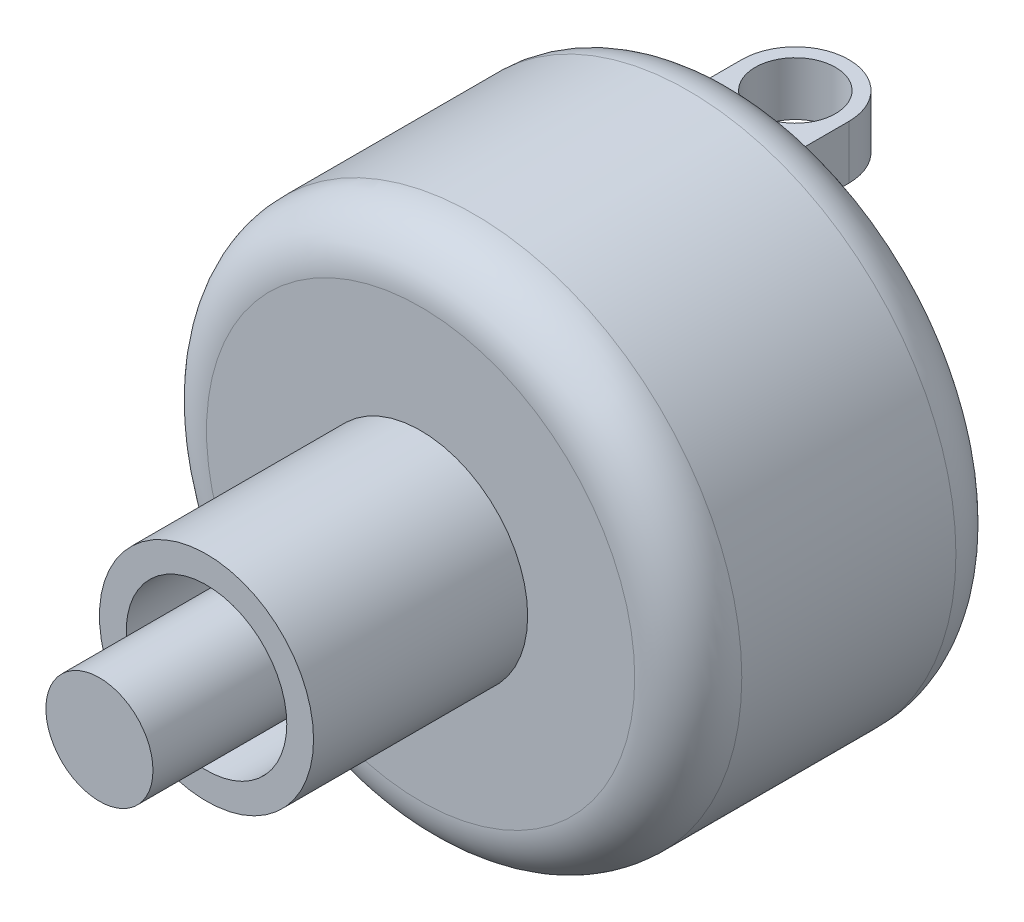
SolidWorks part; units mm, degrees
ref_plane "Front Plane" through (0, 0, 0) normal (0, 0, 1) x (1, 0, 0)
ref_plane "Top Plane" through (0, 0, 0) normal (0, 1, 0) x (1, 0, 0)
ref_plane "Right Plane" through (0, 0, 0) normal (1, 0, 0) x (0, 0, -1)
sketch "Sketch1" plane through (0, 0, 0) normal (0, 0, 1) x (1, 0, 0)
  circle A0 centre (0, 0) radius 25
  dimension "D1" = 50
extrude "Boss-Extrude1" add sketch "Sketch1" along normal blind 30
sketch "Sketch2" plane through (0, 0, 30) normal (0, 0, 1) x (1, 0, 0)
  circle A0 centre (0, 0) radius 10
  dimension "D1" = 20
extrude "Boss-Extrude2" add sketch "Sketch2" along normal blind 20
sketch "Sketch3" plane through (0, 0, 50) normal (0, 0, 1) x (1, 0, 0)
  circle A0 centre (0, 0) radius 7.5
  dimension "D1" = 15
extrude "Cut-Extrude1" cut sketch "Sketch3" against normal blind 20
sketch "Sketch4" plane through (0, 0, 30) normal (0, 0, 1) x (1, 0, 0)
  circle A0 centre (0, 0) radius 5
  dimension "D1" = 10
extrude "Boss-Extrude3" add sketch "Sketch4" along normal blind 30
sketch "Sketch5" plane through (0, 0, 0) normal (0, 0, -1) x (-1, 0, 0)
  circle A0 centre (0, 0) radius 7.5
  dimension "D1" = 15
extrude "Boss-Extrude4" add sketch "Sketch5" along normal blind 5
sketch "Sketch7" plane through (0, 0, 0) normal (0, 0, -1) x (-1, 0, 0)
  line L1 (5, 15) -> (-5, 15)
  line L2 (5, 15) -> (5, 20)
  line L3 (5, 20) -> (-5, 20)
  line L4 (-5, 15) -> (-5, 20)
  line L5 (5, -20) -> (-5, -20)
  line L6 (5, -20) -> (5, -15)
  line L7 (5, -15) -> (-5, -15)
  line L8 (-5, -20) -> (-5, -15)
  point P8 (0, 15)
  point P10 (0, -15)
  dimension "D1" = 5
  dimension "D2" = 10
  dimension "D3" = 10
  dimension "D4" = 5
  dimension "D5" = 15
  dimension "D6" = 15
extrude "Boss-Extrude5" add sketch "Sketch7" along normal blind 10
sketch "Sketch8" plane through (0, 20, 0) normal (0, 1, 0) x (1, 0, 0)
  line L0 (-5, 10) -> (5, 10) construction
  line L1 (5, 10) -> (5, 0) construction
  circle A0 centre (0, 5) radius 3.75
  dimension "D2" = 7.5
  dimension "D1" = 5
  dimension "D3" = 5
extrude "Cut-Extrude2" cut sketch "Sketch8" against normal up to surface (5 mm away) up to face at (0, 15, -5)
sketch "Sketch9" plane through (0, -20, 0) normal (0, -1, 0) x (-1, 0, 0)
  line L0 (5, 10) -> (5, 0) construction
  line L1 (-5, 10) -> (5, 10) construction
  circle A0 centre (0, 5) radius 3.75
  dimension "D1" = 7.5
  dimension "D2" = 5
  dimension "D3" = 5
extrude "Cut-Extrude3" cut sketch "Sketch9" against normal up to surface (5 mm away) up to face at (0, -15, -5)
fillet "Fillet1" radius 5 2 edges at (25, 0, 30) (25, 0, 0)
fillet "Fillet2" radius 5 4 edges at (5, -17.5, -10) (-5, -17.5, -10) (5, 17.5, -10) (-5, 17.5, -10)
fillet "Fillet3" radius 1 2 edges at (-7.5, 0, 0) (-7.5, 0, -5)
